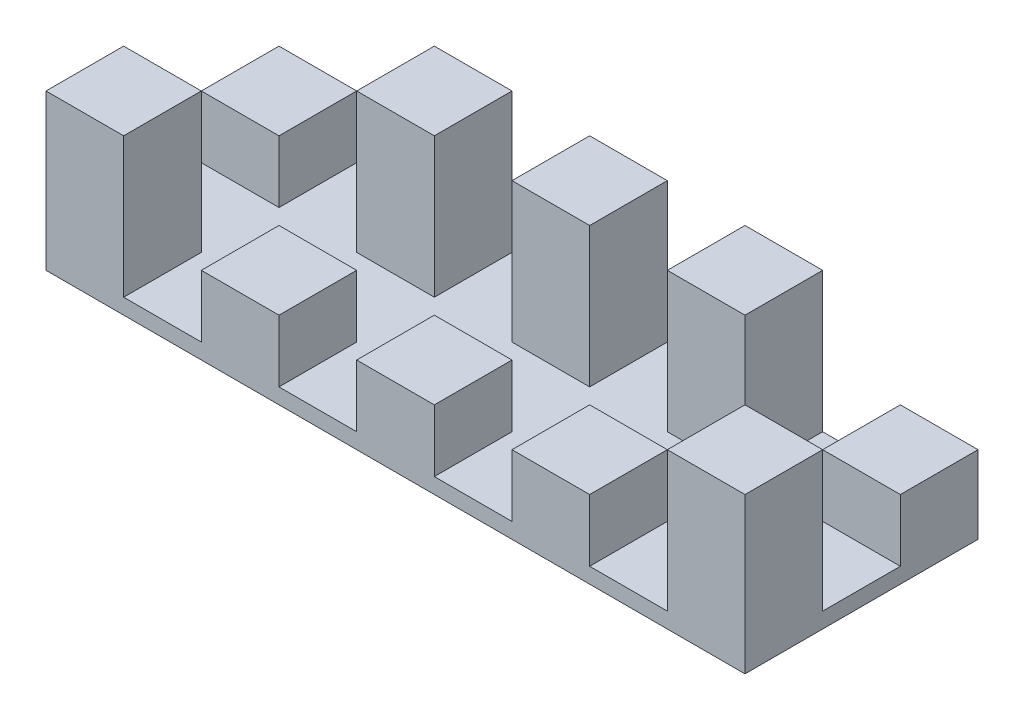
SolidWorks part; units mm, degrees
ref_plane "Front Plane" through (0, 0, 0) normal (0, 0, 1) x (1, 0, 0)
ref_plane "Top Plane" through (0, 0, 0) normal (0, 1, 0) x (1, 0, 0)
ref_plane "Right Plane" through (0, 0, 0) normal (1, 0, 0) x (0, 0, -1)
sketch "Sketch2" plane through (0, 0, 0) normal (0, 1, 0) x (1, 0, 0)
  line L0 (1000, 1500) -> (1000, 1000)
  line L1 (0, 0) -> (4500, 0)
  line L2 (0, 0) -> (0, 1500)
  line L3 (0, 1500) -> (4500, 1500)
  line L4 (4500, 0) -> (4500, 1500)
  line L5 (0, 0) -> (4500, 1500) construction
  line L6 (0, 1500) -> (4500, 0) construction
  line L7 (0, 1500) -> (500, 1500)
  line L8 (0, 1500) -> (0, 1000)
  line L9 (0, 1000) -> (500, 1000)
  line L10 (500, 1500) -> (500, 1000)
  line L11 (0, 1500) -> (500, 1000) construction
  line L12 (0, 1000) -> (500, 1500) construction
  line L13 (1000, 1500) -> (1500, 1500)
  line L14 (1500, 1500) -> (1500, 1000)
  line L15 (1000, 1000) -> (1500, 1000)
  line L16 (2000, 1500) -> (2000, 1000)
  line L17 (2000, 1500) -> (2500, 1500)
  line L18 (2500, 1500) -> (2500, 1000)
  line L19 (2000, 1000) -> (2500, 1000)
  line L20 (3000, 1500) -> (3000, 1000)
  line L21 (3000, 1500) -> (3500, 1500)
  line L22 (3500, 1500) -> (3500, 1000)
  line L23 (3000, 1000) -> (3500, 1000)
  line L24 (4000, 1500) -> (4000, 1000)
  line L25 (4000, 1500) -> (4500, 1500)
  line L26 (4500, 1500) -> (4500, 1000)
  line L27 (4000, 1000) -> (4500, 1000)
  line L28 (2250, 750) -> (-1006.797, 750) construction
  line L29 (0, 500) -> (500, 0) construction
  line L30 (0, 0) -> (500, 500) construction
  line L31 (4000, 500) -> (4500, 500)
  line L32 (4500, 0) -> (4500, 500)
  line L33 (4000, 0) -> (4500, 0)
  line L34 (4000, 0) -> (4000, 500)
  line L35 (3000, 500) -> (3500, 500)
  line L36 (3500, 0) -> (3500, 500)
  line L37 (3000, 0) -> (3500, 0)
  line L38 (3000, 0) -> (3000, 500)
  line L39 (2000, 500) -> (2500, 500)
  line L40 (2500, 0) -> (2500, 500)
  line L41 (2000, 0) -> (2500, 0)
  line L42 (2000, 0) -> (2000, 500)
  line L43 (1000, 500) -> (1500, 500)
  line L44 (1500, 0) -> (1500, 500)
  line L45 (1000, 0) -> (1500, 0)
  line L46 (500, 0) -> (500, 500)
  line L47 (0, 500) -> (500, 500)
  line L48 (0, 0) -> (0, 500)
  line L49 (0, 0) -> (500, 0)
  line L50 (0, 0) -> (4500, 0)
  line L51 (1000, 0) -> (1000, 500)
  point P4 (2250, 750)
  point P9 (250, 1250)
  point P46 (250, 250)
  point P47 (-1927.6129, -956.288)
  point P48 (0, 0)
  point P49 (0, 0)
  point P50 (0, 0)
  dimension "D1" = 1500
  dimension "D2" = 4500
  dimension "D3" = 500
  dimension "D5" = 500
  dimension "D4" = 5
extrude "Boss-Extrude1" add sketch "Sketch2" along normal blind 500 contours L51 L1 L44 L43 | L42 L1 L40 L39 | L24 L27 L4 L3 | L8 L9 L10 L7 | L38 L35 L36 L37 region at (4250, 0, -1250) region at (1250, 0, -250) region at (2250, 0, -250)
extrude "Boss-Extrude2" add sketch "Sketch2<3>" along normal blind 1000 separate body contours L47 L2 L1 L46 | L0 L15 L14 L3 | L16 L19 L18 L3 | L20 L23 L22 L3 | L34 L1 L4 L31 region at (1250, 0, -1250) region at (2250, 0, -1250) region at (250, 0, -250) region at (3250, 0, -1250) region at (4250, 0, -250)
sketch "Sketch2<3>" plane through (0, 0, 0) normal (0, 1, 0) x (1, 0, 0) same geometry as "Sketch2"
extrude "Boss-Extrude3" add sketch "Sketch2<4>" along normal blind 100 contours L1 L51 L43 L44 L42 L39 L40 L38 L35 L36 L34 L31 L4 L27 L24 L3 L22 L23 L20 L18 L19 L16 L14 L15 L0 L10 L9 L2 L47 L46 region at (2250, 0, -750)
sketch "Sketch2<4>" plane through (0, 0, 0) normal (0, 1, 0) x (1, 0, 0) same geometry as "Sketch2"
